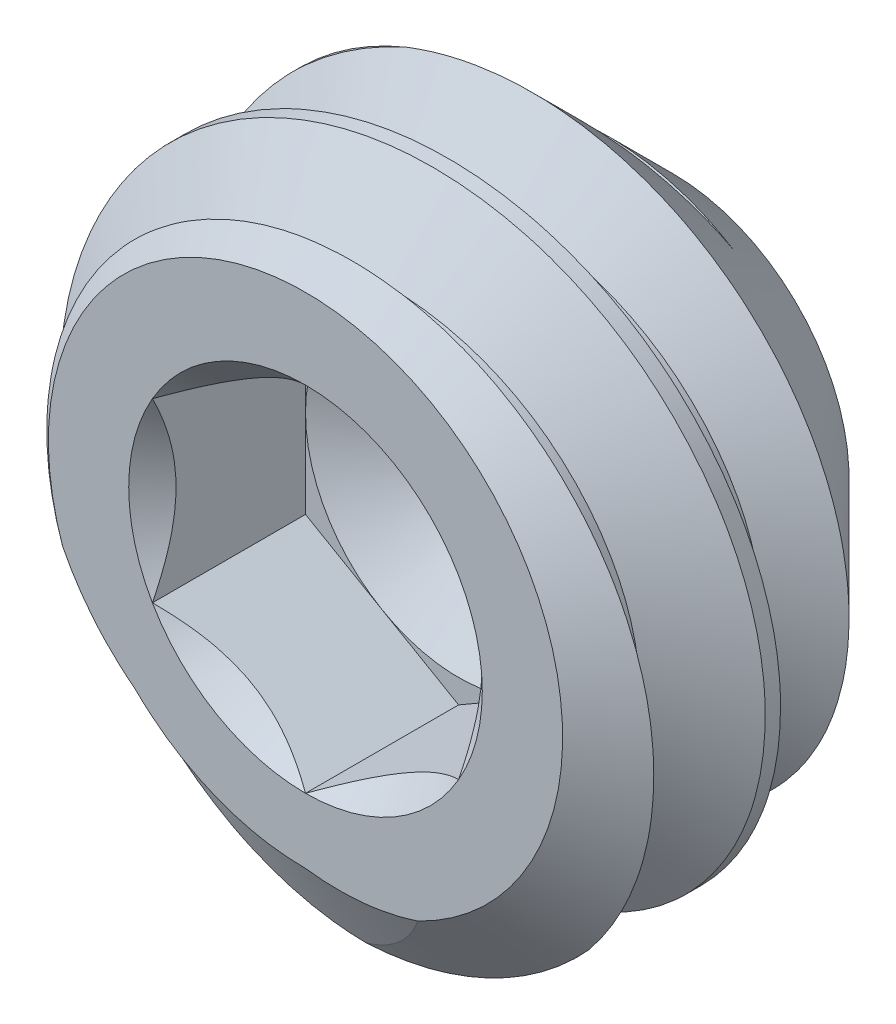
SolidWorks part; units mm, degrees
material "AISI 304"
ref_plane "Front" through (0, 0, 0) normal (0, 0, 1) x (1, 0, 0)
ref_plane "Top" through (0, 0, 0) normal (0, 1, 0) x (1, 0, 0)
ref_plane "Right" through (0, 0, 0) normal (1, 0, 0) x (0, 0, -1)
sketch "Sketch22" plane through (0, 0, 0) normal (1, 0, 0) x (0, 0, -1)
  line L0 (-0.8477, 0) -> (-0.8477, 1.6662)
  line L1 (-0.8477, 1.6662) -> (-0.5561, 2.0828)
  line L2 (-0.5561, 2.0828) -> (0.592, 2.0828)
  line L3 (0.592, 2.0828) -> (1.5335, 1.1413)
  line L4 (1.5335, 1.1413) -> (0.8477, 0)
  line L5 (0.8477, 0) -> (-0.8477, 0)
  line L6 (0.8477, 0) -> (1.5335, 0) construction
  line L7 (1.5335, 0) -> (1.5335, 1.1413) construction
  line L8 (1.5335, -1.1413) -> (0.8477, 0) construction
  line L9 (-0.5561, -2.0828) -> (0.592, -2.0828) construction
  dimension "Dia" = 4.1656
  dimension "Length" = 2.3813
  dimension "D3" = 35
  dimension "D5" = 118
  dimension "D6" = 45
  dimension "D7" = 3.3325
revolve "Revolve1" add sketch "Sketch22" angle 360 about L6
ref_plane "Plane1" through (0, 0, -1.5335) normal (0, 0, 1) x (1, 0, 0)
sketch "Sketch27" plane through (0, 0, -1.5335) normal (0, 0, 1) x (1, 0, 0)
  circle A0 centre (0, 0) radius 2.0828 construction
  circle A1 centre (0, 0) radius 2.0828
curve "Helix/Spiral1" pitch 0.7937 height 3.175 radius 2.0828 centre (0, 0, -1.5335) axis (0, 0, 1) start towards (0, 1, 0)
sketch "Sketch28" plane through (0, 0, 0) normal (1, 0, 0) x (0, 0, -1)
  line L0 (1.5335, 2.0828) -> (2.228, 2.0828)
  line L1 (2.228, 2.0828) -> (1.9304, 1.5672)
  line L2 (1.9304, 1.5672) -> (1.8312, 1.5672)
  line L3 (1.8312, 1.5672) -> (1.5335, 2.0828)
  line L4 (1.6823, 1.825) -> (2.0792, 1.825) construction
  line L6 (-0.5561, 2.0828) -> (0.592, 2.0828) construction
  line L7 (1.5335, 2.2911) -> (1.5335, -2.2911) construction
  dimension "D1" = 0.0992
  dimension "D3" = 60
  dimension "D2" = 0.3969
sweep "Cut-Sweep2" cut profiles "Sketch28" path "Helix/Spiral1" align with end faces yes
sketch "Sketch23" plane through (0, 0, 0.8477) normal (0, 0, 1) x (1, 0, 0)
  line L1 (0, 1.1457) -> (-0.9922, 0.5728)
  line L2 (-0.9922, 0.5728) -> (-0.9922, -0.5728)
  line L3 (-0.9922, -0.5728) -> (0, -1.1457)
  line L4 (0, -1.1457) -> (0.9922, -0.5728)
  line L5 (0.9922, -0.5728) -> (0.9922, 0.5728)
  line L6 (0.9922, 0.5728) -> (0, 1.1457)
  circle A0 centre (0, 0) radius 0.9922 construction
  dimension "Hex" = 1.9844
extrude "Cut-Extrude10" cut sketch "Sketch23" against normal blind 0.9922
sketch "Sketch24" plane through (0, 0, 0.8477) normal (0, 0, 1) x (1, 0, 0)
  circle A0 centre (0, 0) radius 1.1457
extrude "Cut-Extrude11" cut sketch "Sketch24" against normal through all draft 45
sketch "Sketch26" plane through (0, 0, -0.1444) normal (0, 0, 1) x (1, 0, 0)
  circle A0 centre (0, 0) radius 0.9922 construction
  circle A1 centre (0, 0) radius 0.9922
extrude "Cut-Extrude12" cut sketch "Sketch26" against normal through all draft 60
sketch "Sketch30" plane through (0, 0, 0) normal (1, 0, 0) x (0, 0, -1)
  line L0 (-0.5561, 2.0828) -> (0.592, 2.0828) construction
  line L1 (-0.8477, 0) -> (-0.8477, 1.6662) construction
  line L2 (1.5335, 0) -> (1.5335, 1.1413) construction
  line L3 (-0.5561, -2.0828) -> (0.592, -2.0828) construction
  point P0 (-0.8477, 2.0828)
  point P1 (1.5335, 2.0828)
  point P2 (1.5335, -2.0828)
  point P11 (-0.4509, -2.0828)
  dimension "D1" = 1.9844
sketch "Sketch31" plane through (0, 0, 0) normal (1, 0, 0) x (0, 0, -1)
  line L2 (0.8477, 0) -> (1.5335, -1.1413)
  line L3 (1.5335, 1.1413) -> (0.8477, 0)
equation "\"D7@Sketch22\"=\"Dia@Sketch22\"*.8"
equation "\"D1@Sketch28\" = \"D4@Helix/Spiral1\" * .125"
equation "\"D3@Helix/Spiral1\" = \"Length@Sketch22\" + \"D4@Helix/Spiral1\""
equation "\"D1@Sketch30\" = \"D4@Helix/Spiral1\" * 2.5"
equation "\"hex Depth@Cut-Extrude10\" = \"Hex@Sketch23\" * .5"
equation "\"D2@Sketch28\" = \"D4@Helix/Spiral1\" * .5"
